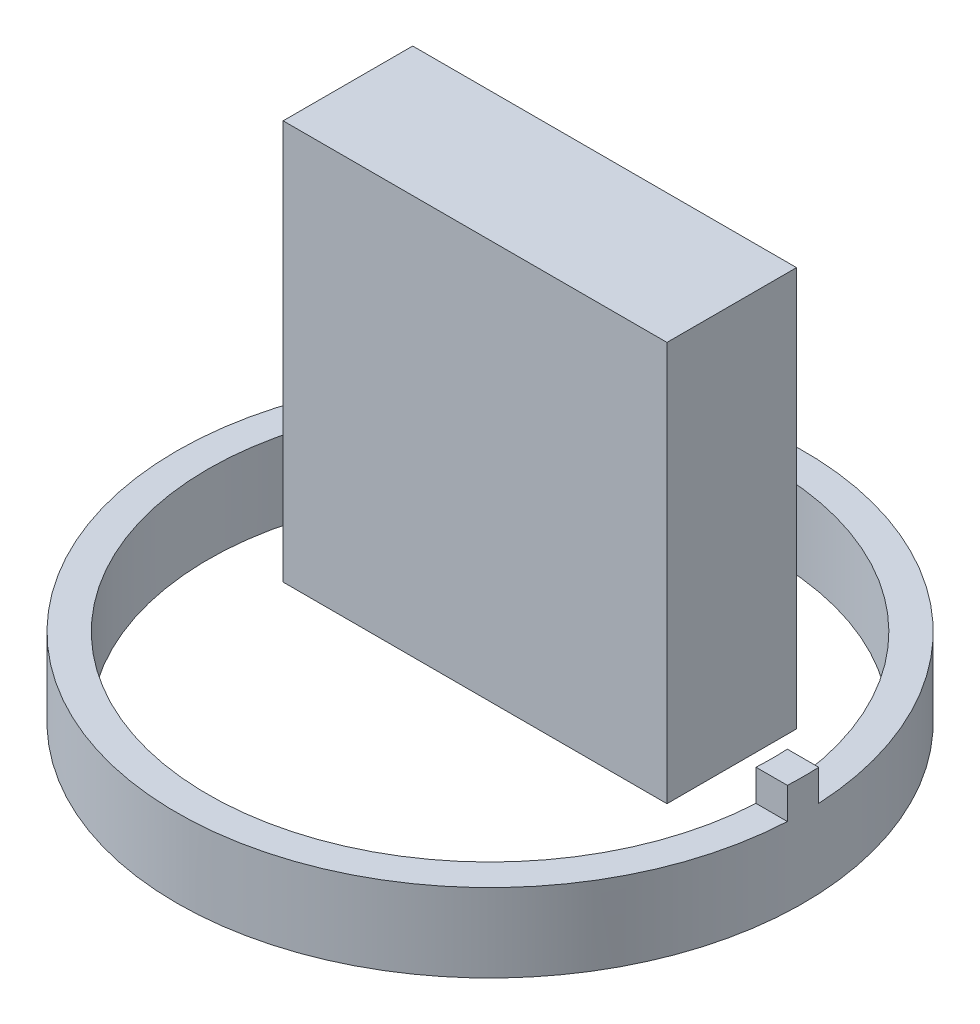
SolidWorks part; units mm, degrees
ref_plane "Front Plane" through (0, 0, 0) normal (0, 0, 1) x (1, 0, 0)
ref_plane "Top Plane" through (0, 0, 0) normal (0, 1, 0) x (1, 0, 0)
ref_plane "Right Plane" through (0, 0, 0) normal (1, 0, 0) x (0, 0, -1)
sketch "Sketch1" plane through (0, 0, 0) normal (0, 1, 0) x (1, 0, 0)
  line L0 (25.4, 0) -> (-25.4, 0) construction
  line L1 (22.8247, 1.27) -> (25.3682, 1.27)
  line L2 (-18.2254, 11.9526) -> (12.8896, 11.9526)
  line L3 (-18.2254, 11.9526) -> (-18.2254, 1.4497)
  line L4 (-18.2254, 1.4497) -> (12.8896, 1.4497)
  line L5 (12.8896, 11.9526) -> (12.8896, 1.4497)
  line L6 (22.8247, -1.27) -> (25.3682, -1.27)
  circle A0 centre (0, 0) radius 27.6225 construction
  circle A1 centre (0, 0) radius 25.4
  circle A4 centre (0, 0) radius 22.86
  dimension "D1" = 55.245
  dimension "D2" = 2.2225
  dimension "D4" = 10.5029
  dimension "D5" = 2.54
  dimension "D3" = 31.115
  dimension "D6" = 1.27
  dimension "D7" = 1.27
extrude "Boss-Extrude1" add sketch "Sketch1" along normal blind 32.385 contours L3 L2 L5 L4
extrude "Boss-Extrude4" add sketch "Sketch1<8>" along normal blind 6.35 separate body contours A1 | A4
sketch "Sketch1<8>" plane through (0, 0, 0) normal (0, 1, 0) x (1, 0, 0) same geometry as "Sketch1"
extrude "Boss-Extrude5" add sketch "Sketch1<9>" along normal blind 2.54 from surface contours A4 L6 A1 L1 region at (24.1188, 0, 0) starting at face at (0, 6.35, 25.4)
sketch "Sketch1<9>" plane through (0, 0, 0) normal (0, 1, 0) x (1, 0, 0) same geometry as "Sketch1"
